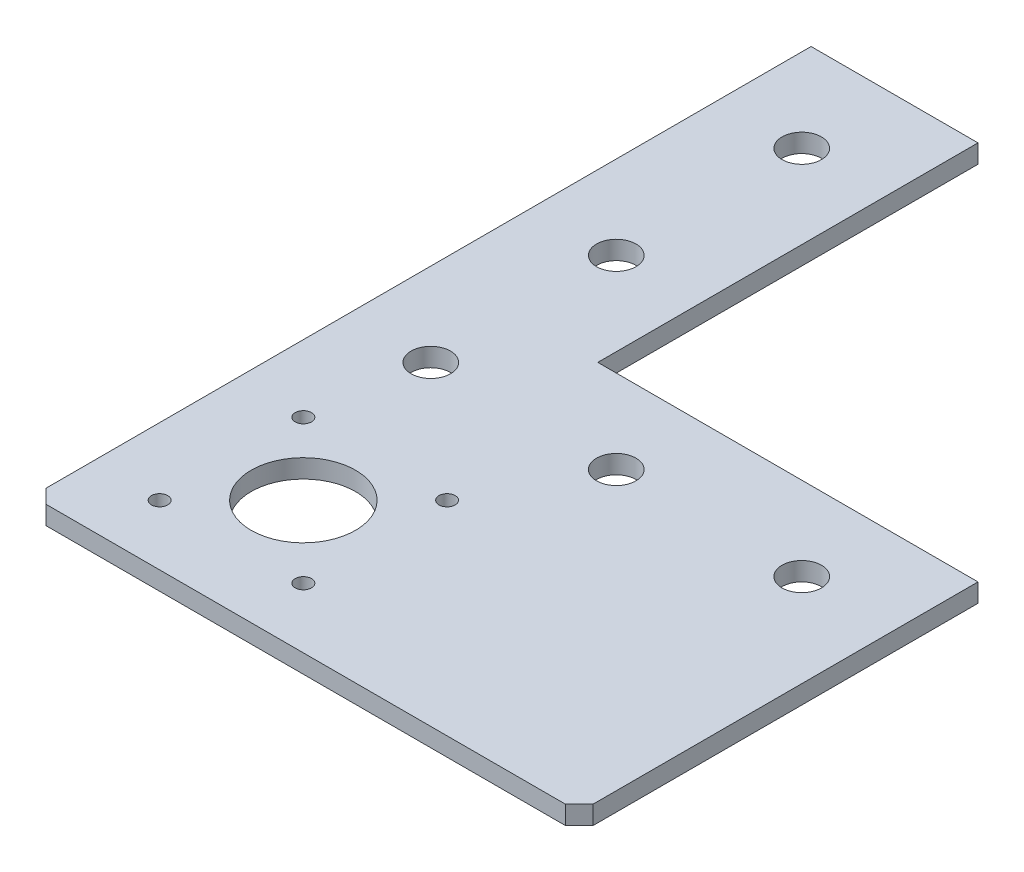
SolidWorks part; units mm, degrees
ref_plane "Front Plane" through (0, 0, 0) normal (0, 0, 1) x (1, 0, 0)
ref_plane "Top Plane" through (0, 0, 0) normal (0, 1, 0) x (1, 0, 0)
ref_plane "Right Plane" through (0, 0, 0) normal (1, 0, 0) x (0, 0, -1)
sketch "Sketch1" plane through (0, 0, 0) normal (0, 1, 0) x (1, 0, 0)
  line L0 (-30, -30) -> (-30, -80)
  line L1 (-30, -30) -> (88.0246, -30.073)
  line L4 (-30, -30) -> (-30, 88)
  line L5 (-30, 88) -> (6, 88)
  line L6 (88, -30) -> (88, 6)
  line L8 (-30, -80) -> (88, -80)
  line L9 (88, -80) -> (88, -30)
  line L10 (88, -30) -> (88.0246, -30.073)
  line L11 (88, 6) -> (6, 6)
  line L12 (6, 6) -> (6, 88)
  circle A0 centre (-12, -12.0111) radius 4.25
  circle A1 centre (28, -12.0111) radius 4.25
  circle A2 centre (68, -12.0111) radius 4.25
  circle A3 centre (-12, 27.9889) radius 4.25
  circle A4 centre (-12, 67.9889) radius 4.25
  circle A5 centre (-15.5, -36) radius 1.75
  circle A6 centre (15.5, -36) radius 1.75
  circle A7 centre (-15.5, -67) radius 1.75
  circle A8 centre (15.5, -67) radius 1.75
  circle A9 centre (0, -51.5) radius 11.25
  dimension "D6" = 8.5
  dimension "D7" = 18
  dimension "D10" = 50
  dimension "D11" = 18
  dimension "D12" = 14.5
  dimension "D5" = 22.5
  dimension "D15" = 3.5
  dimension "D1" = 36
  dimension "D2" = 118
  dimension "D3" = 36
  dimension "D4" = 2
  dimension "D16" = 118
  dimension "D8" = 3
  dimension "D9" = 3
  dimension "D14" = 2
extrude "Boss-Extrude1" add sketch "Sketch1" along normal blind 4
extrude "Boss-Extrude2" add sketch "Sketch1<3>" along normal blind 4 contours L8 L9 L0 A9 A8 A7 A6 A5 region at (31.3009, 0, 55.2993)
sketch "Sketch1<3>" plane through (0, 0, 0) normal (0, 1, 0) x (1, 0, 0) same geometry as "Sketch1"
chamfer "Chamfer1" distance 3 angle 45 2 edges at (88, 2, 80) (-30, 2, 80)
